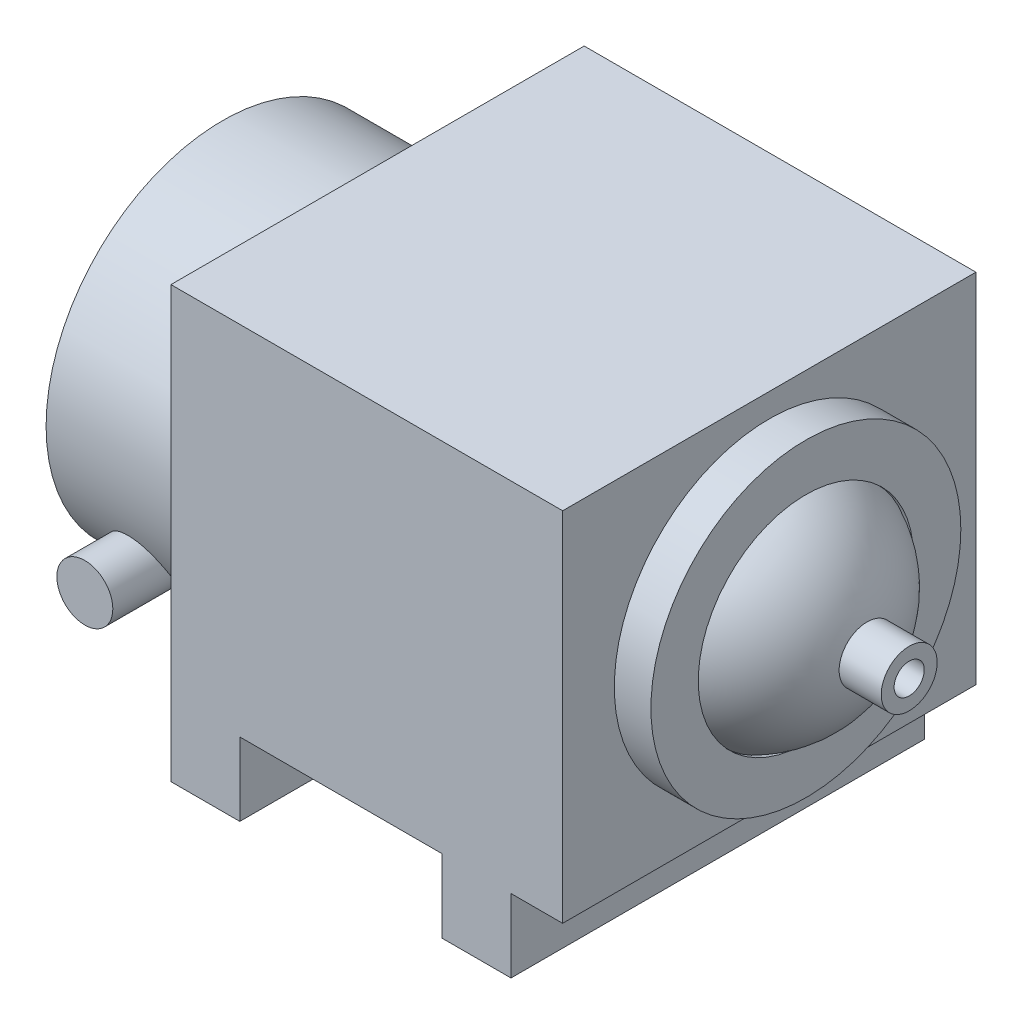
SolidWorks part; units mm, degrees
ref_plane "Front Plane" through (0, 0, 0) normal (0, 0, 1) x (1, 0, 0)
ref_plane "Top Plane" through (0, 0, 0) normal (0, 1, 0) x (1, 0, 0)
ref_plane "Right Plane" through (0, 0, 0) normal (1, 0, 0) x (0, 0, -1)
sketch "Sketch1" plane through (0, 0, 0) normal (0, 1, 0) x (1, 0, 0)
  line L0 (-23.5, 48) -> (-23.5, -48)
  line L1 (-32, -40.5) -> (32, -40.5) construction
  line L2 (-32, -40.5) -> (-32, 40.5) construction
  line L3 (-32, 40.5) -> (32, 40.5) construction
  line L4 (32, -40.5) -> (32, 40.5) construction
  line L5 (-32, -40.5) -> (32, 40.5) construction
  line L6 (-32, 40.5) -> (32, -40.5) construction
  line L7 (-39.5, 48) -> (-23.5, 48)
  line L8 (-39.5, 48) -> (-39.5, -48)
  line L9 (-39.5, -48) -> (-23.5, -48)
  line L10 (39.5, 48) -> (39.5, -48)
  line L11 (-39.5, 48) -> (39.5, -48) construction
  line L12 (-39.5, -48) -> (39.5, 48) construction
  line L13 (23.5, -48) -> (23.5, 48)
  line L14 (23.5, 48) -> (39.5, 48)
  line L15 (23.5, -48) -> (39.5, -48)
  circle A0 centre (-32, 40.5) radius 3
  circle A1 centre (32, 40.5) radius 3
  circle A2 centre (32, -40.5) radius 3
  circle A3 centre (-32, -40.5) radius 3
  point P0 (0, 0)
  point P10 (0, 0)
  dimension "D1" = 6
  dimension "D2" = 6
  dimension "D3" = 6
  dimension "D4" = 6
  dimension "D5" = 64
  dimension "D6" = 81
  dimension "D7" = 79
  dimension "D8" = 96
  dimension "D9" = 16
  dimension "D10" = 16
extrude "Boss-Extrude1" add sketch "Sketch1" along normal blind 17
sketch "Sketch2" plane through (0, 17, 0) normal (0, 1, 0) x (1, 0, 0)
  line L1 (-39.5, -48) -> (51.5, -48)
  line L2 (-39.5, -48) -> (-39.5, 48)
  line L3 (-39.5, 48) -> (51.5, 48)
  line L4 (51.5, -48) -> (51.5, 48)
  dimension "D1" = 91
  dimension "D2" = 96
extrude "Boss-Extrude2" add sketch "Sketch2" along normal blind 83
sketch "Sketch3" plane through (-39.5, 0, 0) normal (-1, 0, 0) x (0, 0, 1)
  line L0 (0, 50) -> (-48, 50) construction
  line L1 (-48, 100) -> (-48, 0) construction
  line L2 (0, 50) -> (48, 50) construction
  line L3 (48, 100) -> (48, 0) construction
  line L4 (0, 0) -> (0, 50) construction
  line L5 (0, 50) -> (0, 100) construction
  line L6 (-48, 100) -> (48, 100) construction
  circle A0 centre (0, 50) radius 41
  dimension "D1" = 82
extrude "Boss-Extrude3" add sketch "Sketch3" along normal blind 36
sketch "Sketch4" plane through (0, 0, 48) normal (0, 0, 1) x (1, 0, 0)
  line L0 (-39.5, 100) -> (-39.5, 0) construction
  line L1 (-39.5, 0) -> (-23.5, 0) construction
  circle A0 centre (-59.5, 28) radius 6.5
  dimension "D1" = 13
  dimension "D2" = 20
  dimension "D3" = 28
extrude "Boss-Extrude4" add sketch "Sketch4" against normal up to next
sketch "Sketch5" plane through (51.5, 0, 0) normal (1, 0, 0) x (0, 0, -1)
  line L0 (-48, 58.5) -> (0, 58.5) construction
  line L1 (-48, 100) -> (-48, 17) construction
  line L2 (0, 58.5) -> (48, 58.5) construction
  line L3 (48, 100) -> (48, 17) construction
  line L4 (0, 100) -> (0, 58.5) construction
  line L5 (-48, 100) -> (48, 100) construction
  line L6 (0, 58.5) -> (0, 17) construction
  line L7 (-48, 17) -> (48, 17) construction
  circle A0 centre (0, 58.5) radius 36
  dimension "D1" = 72
extrude "Boss-Extrude5" add sketch "Sketch5" along normal blind 8.5
sketch "Sketch6" plane through (60, 0, 0) normal (1, 0, 0) x (0, 0, -1)
  circle A0 centre (0, 58.5) radius 25
  dimension "D1" = 50
extrude "Cut-Extrude1" cut sketch "Sketch6" against normal blind 1
dome "Dome1" faces to dome 1 distance 16 reverse direction no elliptical dome no face at (59, 58.5, -25) parameters "D1"=16
ref_plane "Plane1" through (75, 0, 0) normal (1, 0, 0) x (0, 0, -1)
sketch "Sketch7" plane through (75, 0, 0) normal (1, 0, 0) x (0, 0, -1)
  circle A0 centre (0, 58.5) radius 6.5
  circle A1 centre (0, 58.5) radius 3.5
  dimension "D1" = 13
  dimension "D2" = 7
extrude "Boss-Extrude6" add sketch "Sketch7" along normal mid plane 18
